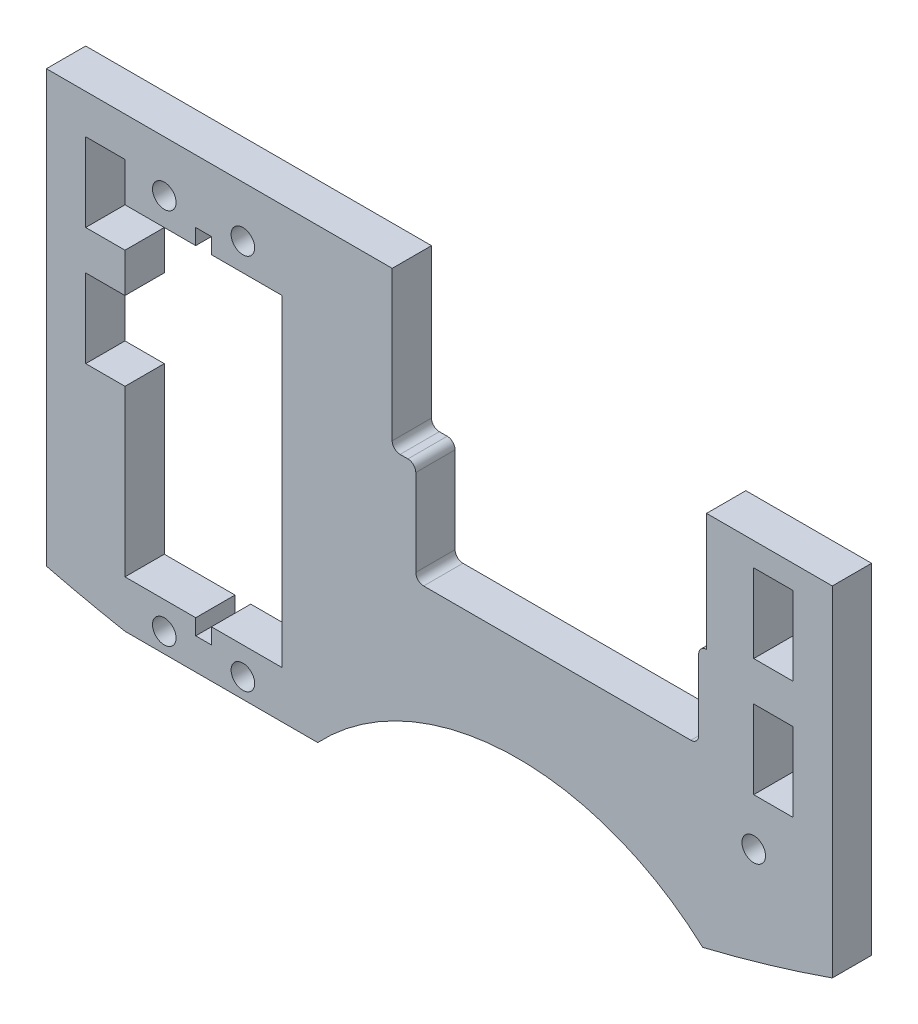
SolidWorks part; units mm, degrees
ref_plane "Plan de face" through (0, 0, 0) normal (0, 0, 1) x (1, 0, 0)
ref_plane "Plan de dessus" through (0, 0, 0) normal (0, 1, 0) x (1, 0, 0)
ref_plane "Plan de droite" through (0, 0, 0) normal (1, 0, 0) x (0, 0, -1)
sketch "Esquisse1" plane through (0, 0, 0) normal (0, 0, 1) x (1, 0, 0)
  line L0 (20, 67) -> (20, -4) construction
  line L1 (0, 0) -> (34.5245, 0)
  line L2 (0, 0) -> (0, 57)
  line L3 (0, 57) -> (44, 57)
  line L4 (100, 0) -> (100, 50)
  line L5 (10, 26.5) -> (30, 26.5) construction
  line L6 (10, 47) -> (19, 47)
  line L7 (10, 42) -> (10, 37)
  line L8 (10, 6) -> (19, 6)
  line L9 (30, 47) -> (30, 6)
  line L10 (20, 16) -> (90, 16) construction
  line L11 (85.4755, 0) -> (100, 0)
  line L12 (21, 4) -> (21, 6)
  line L13 (19, 49) -> (21, 49)
  line L14 (19, 49) -> (19, 47)
  line L15 (21, 6) -> (30, 6)
  line L16 (21, 49) -> (21, 47)
  line L17 (19, 4) -> (21, 4)
  line L18 (19, 4) -> (19, 6)
  line L19 (21, 47) -> (30, 47)
  line L20 (10, 27) -> (10, 6)
  line L21 (90, 47) -> (95, 47)
  line L22 (90, 47) -> (90, 37)
  line L23 (90, 37) -> (95, 37)
  line L24 (95, 47) -> (95, 37)
  line L25 (90, 32) -> (95, 32)
  line L26 (90, 32) -> (90, 22)
  line L27 (90, 22) -> (95, 22)
  line L28 (95, 32) -> (95, 22)
  line L29 (5, 52) -> (10, 52)
  line L30 (5, 52) -> (5, 42)
  line L31 (5, 42) -> (10, 42)
  line L32 (10, 52) -> (10, 47)
  line L33 (5, 37) -> (10, 37)
  line L34 (5, 37) -> (5, 27)
  line L35 (5, 27) -> (10, 27)
  line L36 (84, 50) -> (100, 50)
  line L37 (47, 37) -> (44, 37)
  line L38 (84, 50) -> (84, 35)
  line L39 (84, 35) -> (83, 35)
  line L40 (44, 57) -> (44, 37)
  line L42 (83, 35) -> (83, 24)
  line L43 (83, 24) -> (47, 24)
  line L44 (47, 37) -> (47, 24)
  circle A0 centre (15, 2.5) radius 1.5
  circle A1 centre (25, 2.5) radius 1.5
  circle A2 centre (25, 50.5) radius 1.5
  circle A3 centre (15, 50.5) radius 1.5
  circle A4 centre (20, 16) radius 1.5 construction
  circle A5 centre (20, 16) radius 1.5 construction
  circle A6 centre (90, 16) radius 1.5
  circle A7 centre (60, -24) radius 35 construction
  arc A8 (34.5245, 0) -> (85.4755, 0) centre (60, -24) cw
  dimension "D6" = 3.5
  dimension "D8" = 3
  dimension "D9" = 3
  dimension "D10" = 70
  dimension "D13" = 70
  dimension "D16" = 2
  dimension "D1" = 6
  dimension "D2" = 41
  dimension "D3" = 20
  dimension "D4" = 10
  dimension "D5" = 100
  dimension "D7" = 5
  dimension "D11" = 10
  dimension "D12" = 10
  dimension "D14" = 40
  dimension "D15" = 40
  dimension "D17" = 2
  dimension "D18" = 5
  dimension "D19" = 5
  dimension "D20" = 10
  dimension "D21" = 3
  dimension "D22" = 5
  dimension "D23" = 5
  dimension "D24" = 10
  dimension "D25" = 6
  dimension "D26" = 20
  dimension "D27" = 40
  dimension "D28" = 1
  dimension "D29" = 36
  dimension "D30" = 5
  dimension "D31" = 15
  dimension "D32" = 11
  dimension "D33" = 5
  dimension "D34" = 50
extrude "Boss.-Extru.1" add sketch "Esquisse1" along normal blind 5
fillet "Congé1" radius 1 5 edges at (83, 35, 2.5) (83, 24, 2.5) (47, 24, 2.5) (47, 37, 2.5) (44, 37, 2.5)
sketch "Esquisse2" plane through (0, 0, 5) normal (0, 0, 1) x (1, 0, 0)
  line L0 (0, 0) -> (34.5245, 0) construction
  line L1 (10, 27) -> (10, 6) construction
  line L2 (-40.4936, 0.9705) -> (-34.879, 14.9208)
  line L3 (159.5405, 42.1102) -> (167.1741, 28.8302)
  arc A0 (-34.879, 14.9208) -> (159.5405, 42.1102) centre (42.2645, 172) ccw
  arc A1 (-40.4936, 0.9705) -> (167.1741, 28.8302) centre (42.2645, 172) ccw
  point P3 (10, 0)
  dimension "D1" = 175
  dimension "D2" = 15
  dimension "D3" = 172
extrude "Enlèv. mat.-Extru.1" cut sketch "Esquisse2" against normal blind 10
